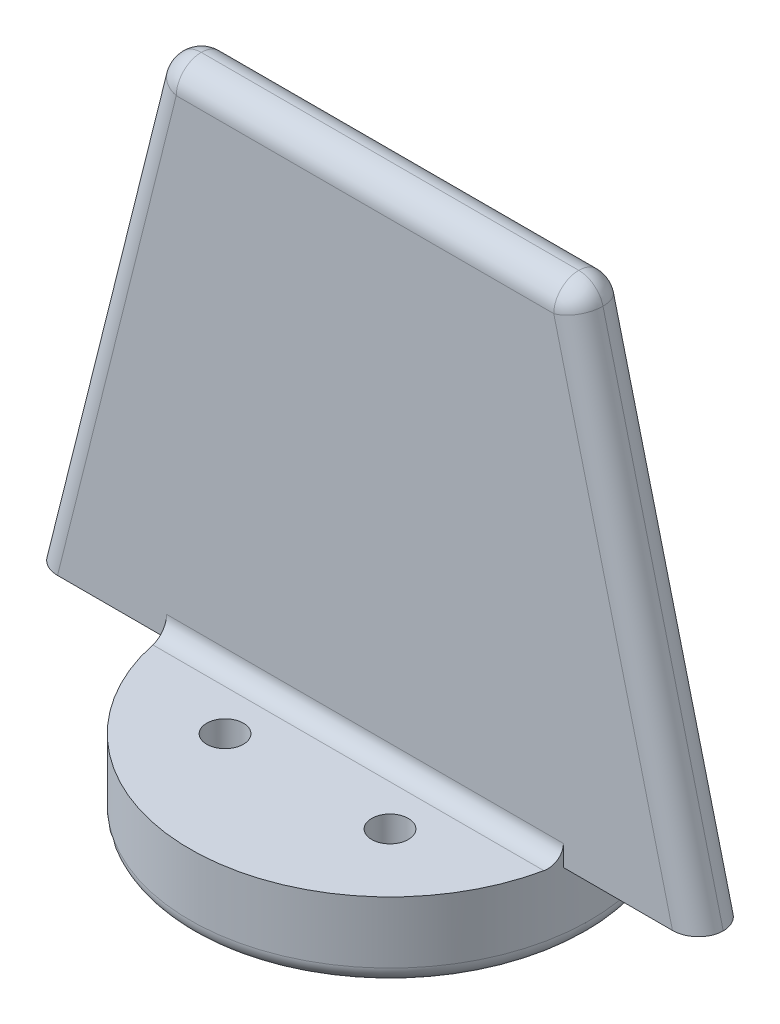
SolidWorks part; units mm, degrees
note: '?' marks a value the reader was unsure of.
ref_plane "Front Plane" through (0, 0, 0) normal (0, 0, 1) x (1, 0, 0)
ref_plane "Top Plane" through (0, 0, 0) normal (0, 1, 0) x (1, 0, 0)
ref_plane "Right Plane" through (0, 0, 0) normal (1, 0, 0) x (0, 0, -1)
sketch "Sketch1" plane through (0, 0, 0) normal (0, 1, 0) x (1, 0, 0)
  line L1 (-20, 1.5) -> (20, 1.5)
  line L2 (-20, 1.5) -> (-20, -1.5)
  line L3 (-20, -1.5) -> (20, -1.5)
  line L4 (20, 1.5) -> (20, -1.5)
  line L5 (0, -1.5) -> (0, 1.5) construction
  line L6 (-20, 0) -> (20, 0) construction
  point P0 (0, 0)
  dimension "D1" = 40
  dimension "D2" = 3
ref_plane "Plane1" through (0, 30, 0) normal (0, 1, 0) x (1, 0, 0)
sketch "Sketch2" plane through (0, 30, 0) normal (0, 1, 0) x (1, 0, 0)
  line L0 (-20, -1.5) -> (20, -1.5) construction
  line L1 (-12.5, 1.5) -> (12.5, 1.5)
  line L2 (-12.5, 1.5) -> (-12.5, -1.5)
  line L3 (-12.5, -1.5) -> (12.5, -1.5)
  line L4 (12.5, 1.5) -> (12.5, -1.5)
  line L5 (0, -1.5) -> (0, 1.5) construction
  line L6 (-12.5, 0) -> (12.5, 0) construction
  point P0 (0, 0)
  dimension "D1" = 25
loft "Loft1" add profiles "Sketch1", "Sketch2"
fillet "Fillet1" radius 1.5 6 edges
sketch "Sketch3" plane through (0, 0, 0) normal (0, -1, 0) x (1, 0, 0)
  circle A0 centre (0, 0) radius 12
  dimension "D1" = 24
extrude "Boss-Extrude1" add sketch "Sketch3" along normal blind 4.45 and the other way blind 0.25
fillet "Fillet2" radius 1 3 edges at (0, -4.45, -12) (0, 0.25, -1.5) (0, 0.25, 1.5)
sketch "Sketch4" plane through (0, -4.45, 0) normal (0, -1, 0) x (1, 0, 0)
  circle A0 centre (0, 0) radius 10
extrude "Cut-Extrude1" cut sketch "Sketch4" against normal blind 2.45
ref_axis "Axis1" through (0, 30, 0) along (0, -1, 0)?
sketch "Sketch8" plane through (0, 0.25, 0) normal (0, 1, 0) x (1, 0, 0)
  circle A1 centre (4.9497, 4.9497) radius 1.1
  point P5 (4.9497, 4.9497)
extrude "Cut-Extrude2" cut sketch "Sketch8" against normal through all
pattern_circular "CirPattern1" count 4 over 360 about axis through (0, 0, 0) along (0, 1, 0) of "Cut-Extrude2"
